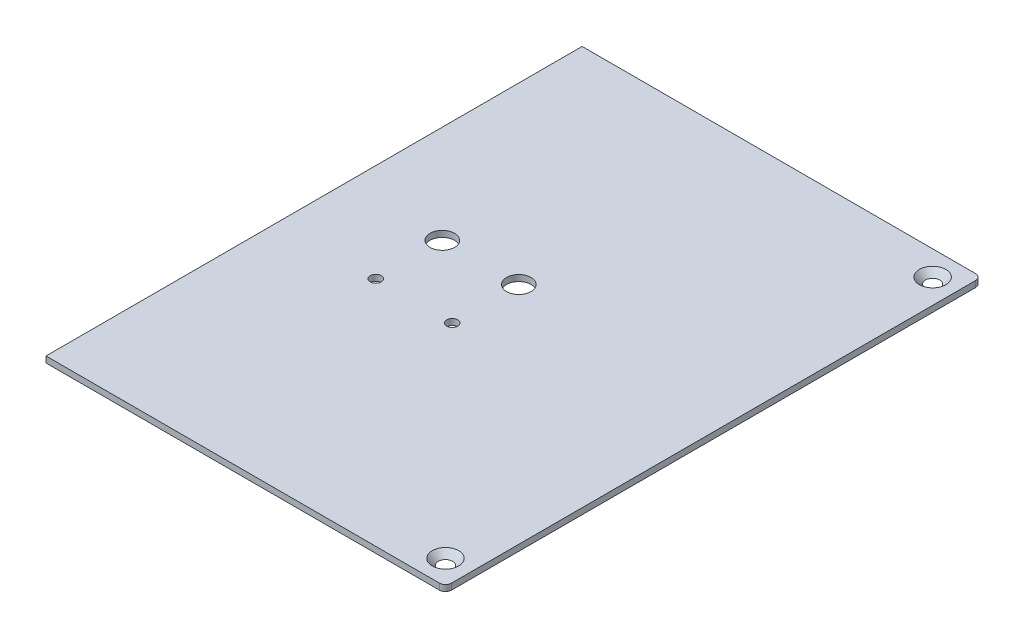
SolidWorks part; units mm, degrees
material "7075-T6, Plate (SS)"
ref_plane "Front Plane" through (0, 0, 0) normal (0, 0, 1) x (1, 0, 0)
ref_plane "Top Plane" through (0, 0, 0) normal (0, 1, 0) x (1, 0, 0)
ref_plane "Right Plane" through (0, 0, 0) normal (1, 0, 0) x (0, 0, -1)
sketch "Sketch1" plane through (0, 0, 0) normal (0, 1, 0) x (1, 0, 0)
  line L1 (-70.2264, 30.9547) -> (44.0736, 30.9547)
  line L2 (-70.2264, 30.9547) -> (-70.2264, -80.2973)
  line L3 (-70.2264, -80.2973) -> (44.0736, -80.2973)
  line L4 (44.0736, 30.9547) -> (44.0736, -80.2973)
  dimension "D1" = 114.3
  dimension "D2" = 111.252
extrude "Boss-Extrude1" add sketch "Sketch1" along normal blind 1.27
hole_wizard "CSK for M2.5 Countersunk Flat Head Screw1" positions "Sketch2" profile "Sketch3" countersink size "M2.5" standard "ISO" end condition up to next
sketch "Sketch2" plane through (0, 1.27, 0) normal (0, 1, 0) x (1, 0, 0)
  line L0 (44.0736, 30.9547) -> (-70.2264, 30.9547) construction
  line L1 (-70.2264, 30.9547) -> (-70.2264, -80.2973) construction
  line L2 (44.0736, -80.2973) -> (44.0736, 30.9547) construction
  line L3 (-70.2264, -80.2973) -> (44.0736, -80.2973) construction
  point P0 (-65.1464, 26.0017)
  point P2 (38.9936, 25.8747)
  point P4 (38.9936, -75.2173)
  point P6 (-65.1464, -75.2173)
  dimension "D1" = 4.953
  dimension "D2" = 5.08
  dimension "D3" = 5.08
  dimension "D4" = 5.08
  dimension "D5" = 5.08
  dimension "D6" = 5.08
  dimension "D7" = 5.08
  dimension "D8" = 5.08
sketch "Sketch3" plane through (-65.1464, 1.27, -26.0017) normal (1, 0, 0) x (0, 0, 1)
  line L0 (0, 0) -> (0, 1.27)
  line L1 (0, 1.27) -> (1.45, 1.27)
  line L2 (1.45, 1.27) -> (1.45, 1.3)
  line L3 (1.45, 1.3) -> (2.75, 0)
  line L5 (2.75, 0) -> (0, 0)
  line L6 (-1.45, 1.3) -> (-2.75, 0) construction
  line L11 (0, -6.35) -> (0, 107.95) construction
  dimension "Thru Hole Dia." = 2.9
  dimension "Thru Hole Depth" = 1.27
  dimension "Near C'Sink Dia." = 5.5
  dimension "Near C'Sink Angle" = 90
fillet "Fillet1" radius 1.27 4 edges at (-70.2264, 0.635, 80.2973) (44.0736, 0.635, 80.2973) (44.0736, 0.635, -30.9547) (-70.2264, 0.635, -30.9547)
sketch "Sketch4" plane through (0, 1.27, 0) normal (0, 1, 0) x (1, 0, 0)
  line L0 (-70.2264, 30.9547) -> (-38.8226, 30.9547)
  line L1 (-70.2264, 29.6847) -> (-70.2264, -79.0273) construction
  line L2 (-38.8226, 30.9547) -> (-38.8226, -80.2973)
  line L3 (-38.8226, -80.2973) -> (-70.2264, -80.2973)
  line L4 (-70.2264, -80.2973) -> (-70.2264, 30.9547)
  line L5 (42.8036, 30.9547) -> (-68.9564, 30.9547) construction
  line L6 (-68.9564, -80.2973) -> (42.8036, -80.2973) construction
  dimension "D1" = 0
  dimension "D2" = 0
extrude "Cut-Extrude1" cut sketch "Sketch4" against normal up to next
sketch "Sketch5" plane through (0, 1.27, 0) normal (0, 1, 0) x (1, 0, 0)
  line L0 (44.0736, -24.6713) -> (-38.8226, -24.6713) construction
  line L1 (44.0736, -79.0273) -> (44.0736, 29.6847) construction
  line L2 (-38.8226, -80.2973) -> (-38.8226, 30.9547) construction
  circle A0 centre (-18.4805, -32.2119) radius 1.143
  circle A1 centre (-2.6055, -32.2119) radius 1.143
  dimension "D4" = 2.286
  dimension "D5" = 2.286
  dimension "D1" = 7.5406
  dimension "D2" = 7.5406
  dimension "D3" = 46.6791
  dimension "D6" = 15.875
extrude "Cut-Extrude2" cut sketch "Sketch5" against normal blind 2.54
sketch "Sketch6" plane through (0, 1.27, 0) normal (0, 1, 0) x (1, 0, 0)
  line L0 (-38.8226, -25.3063) -> (44.0736, -25.3063) construction
  line L1 (-38.8226, -80.2973) -> (-38.8226, 30.9547) construction
  line L2 (44.0736, -79.0273) -> (44.0736, 29.6847) construction
  line L5 (-18.4805, -18.4007) -> (-2.6055, -18.4007) construction
  line L6 (42.8036, 30.9547) -> (-38.8226, 30.9547) construction
  circle A0 centre (-18.4805, -32.2119) radius 1.143 construction
  circle A1 centre (-2.6055, -18.4007) radius 2.54
  circle A2 centre (-18.4805, -18.4007) radius 2.54
  dimension "D1" = 6.9056
  dimension "D3" = 5.08
  dimension "D4" = 5.08
  dimension "D2" = 49.3554
  dimension "D5" = 15.875
  dimension "D6" = 49.3554
  dimension "D7" = 15.875
  dimension "D8" = 46.6791
extrude "Cut-Extrude3" cut sketch "Sketch6" against normal blind 2.54
